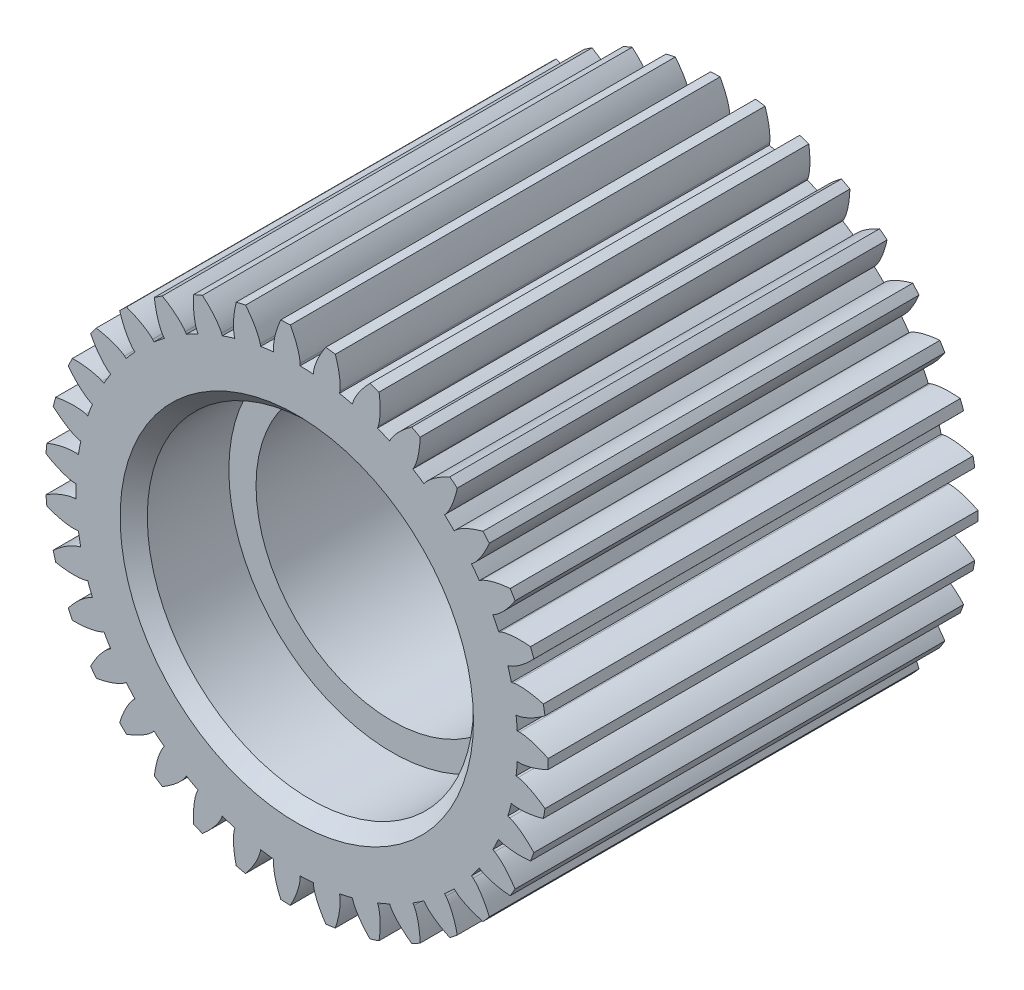
SolidWorks part; units mm, degrees
material "PLA"
ref_plane "Front Plane" through (0, 0, 0) normal (0, 0, 1) x (1, 0, 0)
ref_plane "Top Plane" through (0, 0, 0) normal (0, 1, 0) x (1, 0, 0)
ref_plane "Right Plane" through (0, 0, 0) normal (1, 0, 0) x (0, 0, -1)
sketch "Sketch1" plane through (0, 0, 0) normal (0, 0, 1) x (1, 0, 0)
  circle A0 centre (0, 0) radius 14.25
  dimension "D1" = 28.5
extrude "Boss-Extrude1" add sketch "Sketch1" along normal mid plane 19.8651
sketch "Sketch2" plane through (0, 0, 0) normal (0, 0, 1) x (1, 0, 0)
  line L0 (0, 0) -> (13.7487, 0.1878) construction
  line L1 (0, 0) -> (13.75, 0) construction
  line L2 (0, 0) -> (13.7487, -0.1878) construction
  line L3 (12.9171, -0.1764) -> (13.1238, -0.1792)
  line L4 (12.9196, 0.1764) -> (13.1238, 0.1792)
  circle A0 centre (0, 0) radius 13.75 construction
  circle A1 centre (0, 0) radius 12.9208 construction
  circle A2 centre (0, 0) radius 13.125
  circle A3 centre (0, 0) radius 14.25 construction
  circle A4 centre (0, 0) radius 14.25
  spline S0 degree 4 poles (12.9196, 0.1764) (12.924, 0.1766) (12.9364, 0.1771) (12.9597, 0.1789) (12.9978, 0.183) (13.0462, 0.1897) (13.1086, 0.2003) (13.1818, 0.2152) (13.262, 0.2341) (13.3488, 0.2572) (13.4351, 0.2827) (13.5207, 0.3103) (13.6056, 0.3398) (13.708, 0.3778) (13.8301, 0.4265) (13.9716, 0.4882) (14.1308, 0.5636) (14.2914, 0.6462) (14.448, 0.7322) (14.6046, 0.8246) (14.7548, 0.9177) (14.909, 1.0199) (15.0503, 1.117) (15.2064, 1.2318) (15.3317, 1.3261) (15.4945, 1.4568) (15.5899, 1.5359) (15.7006, 1.6305) (15.7492, 1.6737) (15.7792, 1.7002) knots 0 0 0 0 0 0.005377 0.015084 0.028532 0.04661 0.064855 0.092111 0.119476 0.146842 0.174209 0.201575 0.228941 0.256307 0.307035 0.361767 0.4165 0.471232 0.525964 0.580697 0.635429 0.690161 0.744894 0.799626 0.854358 0.909091 0.954545 1 1 1 1 1 construction
  spline S1 degree 4 poles (12.9196, 0.1764) (12.924, 0.1766) (12.9364, 0.1771) (12.9597, 0.1789) (12.9978, 0.183) (13.0462, 0.1897) (13.1086, 0.2003) (13.1818, 0.2152) (13.262, 0.2341) (13.3488, 0.2572) (13.4351, 0.2827) (13.5207, 0.3103) (13.6056, 0.3398) (13.708, 0.3778) (13.8301, 0.4265) (13.9716, 0.4882) (14.1308, 0.5636) (14.2914, 0.6462) (14.448, 0.7322) (14.6046, 0.8246) (14.7548, 0.9177) (14.909, 1.0199) (15.0503, 1.117) (15.2064, 1.2318) (15.3317, 1.3261) (15.4592, 1.4285) (15.521, 1.479) (15.5524, 1.5052) knots 0 0 0 0 0 0.005377 0.015084 0.028532 0.04661 0.064855 0.092111 0.119476 0.146842 0.174209 0.201575 0.228941 0.256307 0.307035 0.361767 0.4165 0.471232 0.525964 0.580697 0.635429 0.690161 0.744894 0.799626 0.854358 0.909091 0.909091 0.909091 0.909091 0.909091
  spline S2 degree 4 poles (12.9171, -0.1764) (12.9215, -0.1765) (12.9339, -0.1771) (12.9573, -0.1789) (12.9954, -0.1829) (13.0438, -0.1897) (13.1062, -0.2003) (13.1794, -0.2152) (13.2595, -0.234) (13.3464, -0.2572) (13.4326, -0.2827) (13.5182, -0.3103) (13.6031, -0.3397) (13.7055, -0.3777) (13.8276, -0.4265) (13.9692, -0.4882) (14.1283, -0.5635) (14.2889, -0.6462) (14.4456, -0.7322) (14.6021, -0.8245) (14.7524, -0.9177) (14.9065, -1.0199) (15.0479, -1.117) (15.204, -1.2317) (15.3293, -1.3261) (15.492, -1.4568) (15.5874, -1.5358) (15.6981, -1.6305) (15.7468, -1.6737) (15.7768, -1.7002) knots 0 0 0 0 0 0.005377 0.015084 0.028532 0.04661 0.064855 0.092111 0.119476 0.146842 0.174209 0.201575 0.228941 0.256307 0.307035 0.361767 0.4165 0.471232 0.525964 0.580697 0.635429 0.690161 0.744894 0.799626 0.854358 0.909091 0.954545 1 1 1 1 1 construction
  spline S3 degree 4 poles (12.9171, -0.1764) (12.9215, -0.1765) (12.9339, -0.1771) (12.9573, -0.1789) (12.9954, -0.1829) (13.0438, -0.1897) (13.1062, -0.2003) (13.1794, -0.2152) (13.2595, -0.234) (13.3464, -0.2572) (13.4326, -0.2827) (13.5182, -0.3103) (13.6031, -0.3397) (13.7055, -0.3777) (13.8276, -0.4265) (13.9692, -0.4882) (14.1283, -0.5635) (14.2889, -0.6462) (14.4456, -0.7322) (14.6021, -0.8245) (14.7524, -0.9177) (14.9065, -1.0199) (15.0479, -1.117) (15.204, -1.2317) (15.3293, -1.3261) (15.4568, -1.4284) (15.5185, -1.479) (15.5499, -1.5051) knots 0 0 0 0 0 0.005377 0.015084 0.028532 0.04661 0.064855 0.092111 0.119476 0.146842 0.174209 0.201575 0.228941 0.256307 0.307035 0.361767 0.4165 0.471232 0.525964 0.580697 0.635429 0.690161 0.744894 0.799626 0.854358 0.909091 0.909091 0.909091 0.909091 0.909091
  dimension "D1" = 27.5
  dimension "D2" = 25.8415
  dimension "D3" = 26.25
  dimension "D4" = 0.782
  dimension "D5" = 0.782
extrude "Cut-Extrude1" cut sketch "Sketch2" against normal through all both and the other way through all contours A2 A4 region at (13.7878, -0.0005, 0)
pattern_circular "CirPattern2" count 55 over 360 about axis through (0, 0, 9.9326) along (0, 0, -1) of "Cut-Extrude1"
sketch "Sketch3" plane through (0, 0, 9.9326) normal (0, 0, 1) x (1, 0, 0)
  circle A0 centre (0, 0) radius 5
  dimension "D1" = 10
sketch "Sketch4" plane through (0, 0, -9.9326) normal (0, 0, -1) x (-1, 0, 0)
  circle A0 centre (0, 0) radius 9.25
  dimension "D1" = 18.5
extrude "Boss-Extrude2" add sketch "Sketch4" along normal blind 15.8109
sketch "Sketch5" plane through (0, 0, -25.7434) normal (0, 0, -1) x (-1, 0, 0)
  line L0 (0, 0) -> (9.25, 0) construction
  line L1 (0, 0) -> (9.2458, 0.2772) construction
  line L2 (0, 0) -> (9.2458, -0.2772) construction
  line L3 (8.1981, 0.2458) -> (8.1213, 0.2435)
  line L4 (8.1981, -0.2458) -> (8.1213, -0.2435)
  circle A0 centre (0, 0) radius 8.2223 construction
  circle A1 centre (0, 0) radius 8.125
  arc A2 (9.2269, -0.6536) -> (9.2269, 0.6536) centre (0, 0) ccw
  spline S0 degree 4 poles (8.1981, 0.2458) (8.2009, 0.2459) (8.2088, 0.2464) (8.2237, 0.2478) (8.2479, 0.2508) (8.2927, 0.2578) (8.3462, 0.2687) (8.4062, 0.2834) (8.4704, 0.3017) (8.525, 0.3188) (8.5792, 0.3372) (8.633, 0.3569) (8.6977, 0.3821) (8.7749, 0.4144) (8.8643, 0.4551) (8.9648, 0.5047) (9.0661, 0.559) (9.1649, 0.6153) (9.2636, 0.6757) (9.3582, 0.7365) (9.4552, 0.8032) (9.5441, 0.8664) (9.6423, 0.941) (9.721, 1.0024) (9.8232, 1.0872) (9.8831, 1.1385) (9.9525, 1.1999) (9.983, 1.2279) (10.0018, 1.2451) knots 0 0 0 0 0 0.005377 0.015084 0.028532 0.04661 0.092111 0.119476 0.146842 0.174209 0.201575 0.228941 0.256307 0.307035 0.361767 0.4165 0.471232 0.525964 0.580697 0.635429 0.690161 0.744894 0.799626 0.854358 0.909091 0.954545 1 1 1 1 1 construction
  spline S1 degree 4 poles (8.1981, 0.2458) (8.2009, 0.2459) (8.2088, 0.2464) (8.2237, 0.2478) (8.2479, 0.2508) (8.2927, 0.2578) (8.3462, 0.2687) (8.4062, 0.2834) (8.4704, 0.3017) (8.525, 0.3188) (8.5792, 0.3372) (8.633, 0.3569) (8.6977, 0.3821) (8.7749, 0.4144) (8.8643, 0.4551) (8.9648, 0.5047) (9.0661, 0.559) (9.1649, 0.6153) (9.2636, 0.6757) (9.3582, 0.7365) (9.4552, 0.8032) (9.5441, 0.8664) (9.6423, 0.941) (9.721, 1.0024) (9.8011, 1.0688) (9.8398, 1.1016) (9.8596, 1.1186) knots 0 0 0 0 0 0.005377 0.015084 0.028532 0.04661 0.092111 0.119476 0.146842 0.174209 0.201575 0.228941 0.256307 0.307035 0.361767 0.4165 0.471232 0.525964 0.580697 0.635429 0.690161 0.744894 0.799626 0.854358 0.909091 0.909091 0.909091 0.909091 0.909091
  spline S2 degree 4 poles (8.1981, -0.2458) (8.2009, -0.2459) (8.2088, -0.2464) (8.2237, -0.2478) (8.2479, -0.2508) (8.2927, -0.2578) (8.3462, -0.2687) (8.4062, -0.2834) (8.4704, -0.3017) (8.525, -0.3188) (8.5792, -0.3372) (8.633, -0.3569) (8.6977, -0.3821) (8.7749, -0.4144) (8.8643, -0.4551) (8.9648, -0.5047) (9.0661, -0.559) (9.1649, -0.6153) (9.2636, -0.6757) (9.3582, -0.7365) (9.4552, -0.8032) (9.5441, -0.8664) (9.6423, -0.941) (9.721, -1.0024) (9.8232, -1.0872) (9.8831, -1.1385) (9.9525, -1.1999) (9.983, -1.2279) (10.0018, -1.2451) knots 0 0 0 0 0 0.005377 0.015084 0.028532 0.04661 0.092111 0.119476 0.146842 0.174209 0.201575 0.228941 0.256307 0.307035 0.361767 0.4165 0.471232 0.525964 0.580697 0.635429 0.690161 0.744894 0.799626 0.854358 0.909091 0.954545 1 1 1 1 1 construction
  spline S3 degree 4 poles (8.1981, -0.2458) (8.2009, -0.2459) (8.2088, -0.2464) (8.2237, -0.2478) (8.2479, -0.2508) (8.2927, -0.2578) (8.3462, -0.2687) (8.4062, -0.2834) (8.4704, -0.3017) (8.525, -0.3188) (8.5792, -0.3372) (8.633, -0.3569) (8.6977, -0.3821) (8.7749, -0.4144) (8.8643, -0.4551) (8.9648, -0.5047) (9.0661, -0.559) (9.1649, -0.6153) (9.2636, -0.6757) (9.3582, -0.7365) (9.4552, -0.8032) (9.5441, -0.8664) (9.6423, -0.941) (9.721, -1.0024) (9.8011, -1.0688) (9.8398, -1.1016) (9.8596, -1.1186) knots 0 0 0 0 0 0.005377 0.015084 0.028532 0.04661 0.092111 0.119476 0.146842 0.174209 0.201575 0.228941 0.256307 0.307035 0.361767 0.4165 0.471232 0.525964 0.580697 0.635429 0.690161 0.744894 0.799626 0.854358 0.909091 0.909091 0.909091 0.909091 0.909091
  dimension "D2" = 16.25
  dimension "D3" = 18.5
  dimension "D1" = 16.4446
  dimension "D4" = 1.717
  dimension "D5" = 1.717
extrude "Cut-Extrude2" cut sketch "Sketch5" against normal up to surface (15.8109 mm away) contours A2 A1 region at (-8.7837, 0, -25.7434) up to face at (9.25, 0, -9.9326)
pattern_circular "CirPattern3" count 35 over 360 about axis through (0, 0, -25.7434) along (0, 0, 1) of "Cut-Extrude2"
extrude "Cut-Extrude3" cut sketch "Sketch3" against normal through all contours A0
sketch "Sketch7" plane through (0, 0, -25.7434) normal (0, 0, -1) x (-1, 0, 0)
  circle A0 centre (0, 0) radius 6
  dimension "D1" = 12
extrude "Cut-Extrude4" cut sketch "Sketch7" against normal blind 3.5
ref_plane "Plane1" through (0, 0, -7.9054) normal (0, 0, -1) x (-1, 0, 0)
mirror "Mirror1" [suppressed] about plane through (0, 0, -7.9054) normal (0, 0, -1)
sketch "Sketch8" plane through (0, 0, 9.9326) normal (0, 0, 1) x (1, 0, 0)
  circle A0 centre (0, 0) radius 16.2595
extrude "Cut-Extrude5" cut sketch "Sketch8" against normal up to surface (19.8651 mm away) up to face at (0, 0, -9.9326)
ref_plane "Plane2" through (0, 0, -17.838) normal (0, 0, -1) x (-1, 0, 0)
mirror "Mirror3" about plane through (0, 0, -17.838) normal (0, 0, -1) of "Cut-Extrude4"
chamfer "Chamfer1" distance 0.5 angle 45 2 edges at (-6, 0, -25.7434) (-6, 0, -9.9326)
equation "\"module\" = 0.5"
equation "\"pressure angle\" = 20.0"
equation "\"h_a\" = 0.5"
equation "\"h_b\" = 0.625"
equation "\"clr_tip_root\" = 0.125"
equation "\"D1@Sketch1\" = \"dp_p_b\" + 2 * \"h_a\""
equation "\"D1@Boss-Extrude1\"=\"fw_p_b\" -  \"standard_clearance_1_5mm\""
equation "\"D1@Sketch2\" = \"dp_p_b\""
equation "\"D2@Sketch2\"= \"db_p_b\""
equation "\"D3@Sketch2\" = \"dp_p_b\" - 2 * \"h_b\""
equation "\"Nr_s\" = 170"
equation "\"pressure_angle\" = 20.0"
equation "\"h_f\" = 0.625"
equation "\"dp_r_s\" = 85.0"
equation "\"bearing_ID\" = 75"
equation "\"bearing_OD\" = 95"
equation "\"bearing_height\" = 10"
equation "\"clearance_planet\" = 1.5"
equation "\"case_dist\" = 6.5"
equation "\"Motor_case_OD_max\" = 131.3"
equation "\"case_mounting_PCD\" = 123.8"
equation "\"bearing mount thickness\" = 8"
equation "\"case_mounting_hole_dia\" = 3"
equation "\"output_mounting_PCD\" = 103"
equation "\"output_mounting_hole_dia\" = 4"
equation "\"clearance_case_mount_holes_shell_thickness\" = 1"
equation "\"motor_case_OD_base\" = 121.8"
equation "\"sec_carrier_thickness\" = 5"
equation "\"sun_coupler_hub_thickness\" = 4"
equation "\"clearance_sun_coupler_sec_carrier\" = 1.5"
equation "\"clearance_motor_and_case\" = 5"
equation "\"motor_OD\" = 106.8"
equation "\"Motor_case_thickness\" = 2.5"
equation "\"Motor_case_ID\" = 116.8"
equation "\"case_mounting_hole_shift\" = 1.0"
equation "\"output_mounting_nut_wrench_size\" = 7"
equation "\"output_mounting_nut_thickness\" = 3.2"
equation "\"case_mounting_hole_allen_socket_dia\" = 5.5"
equation "\"output_mounting_nut_depth\" = 3"
equation "\"case_mounting_bolt_depth\" = 4.5"
equation "\"Ns\" = 80"
equation "\"ring_radial_thickness\" = 5"
equation "\"ring_to_chamfer_clearance\" = 1.5"
equation "\"Motor_case_OD_base_to_chamfer\" = 5"
equation "\"pattern_offset_from_motor_case_OD_base\" = 3"
equation "\"pattern_bulge_dia\" = 3"
equation "\"pattern_num_bulge\" = 18"
equation "\"pattern_depth\" = 2"
equation "\"motor_height\" = 47.6"
equation "\"case_mounting_wrench_size\" = 5.5"
equation "\"case_mounting_nut_clearance\" = 2"
equation "\"base_plate_thickness\" = 4"
equation "\"case_mounting_nut_thickness\" = 2.4"
equation "\"case_mounting_surface_height\" = 4"
equation "\"motor_mount_hole_PCD\" = 40"
equation "\"motor_mount_hole_dia\" = 5"
equation "\"motor_mount_hole_num\" = 4"
equation "\"central_hole_offset_from_motor_mount_PCD\" = 5"
equation "\"wire_slot_dist_from_center\" = 45.5"
equation "\"wire_slot_length\" = 10"
equation "\"wire_slot_radius\" = 3"
equation "\"driver_upper_holes_dist_from_center\" = 29"
equation "\"driver_lower_holes_dist_from_center\" = 13"
equation "\"driver_side_holes_dist_from_center\" = 22.5"
equation "\"driver_mount_holes_dia\" = 3"
equation "\"driver_mount_inserts_OD\" = 4.8"
equation "\"driver_mount_thickness\" = 1.5"
equation "\"driver_mount_height\" = 6"
equation "\"air_flow_hole_offset\" = 3"
equation "\"num_planet\" = 5"
equation "\"planet_pin_bolt_dia\" = 5"
equation "\"planet_pin_socket_head_dia\" = 8.5"
equation "\"carrier_PCD\" = 67.5"
equation "\"planet_shaft_dia\" = 8"
equation "\"planet_shaft_step_offset\" = 1"
equation "\"carrier_trapezoidal_support_sun_offset\" = 5"
equation "\"carrier_trapezoidal_support_hole_PCD_offset_bearing_ID\" = 4"
equation "\"carrier_trapezoidal_support_hole_dia\" = 3"
equation "\"carrier_trapezoidal_support_hole_socket_head_dia\" = 5.5"
equation "\"carrier_bearing_step_width\" = 1.5"
equation "\"standard_clearance_1_5mm\" = 1.5"
equation "\"standard_fillet_1_5mm\" = 1.5"
equation "\"sun_shaft_bearing_OD\" = 16"
equation "\"sun_shaft_bearing_width\" = 5"
equation "\"standard_bearing_insertion_chamfer\" = 0.5"
equation "\"carrier_trapezoidal_support_hole_wrench_size\" = 5.5"
equation "\"planet_pin_bolt_wrench_size\" = 8"
equation "\"planet_bearing_OD\" = 12"
equation "\"planet_bearing_width\" = 3.5"
equation "\"planet_bore\" = 10"
equation "\"D1@Sketch3\"=\"planet_bore\""
equation "\"Np_b\" = 55"
equation "\"dp_s\" = 40.0"
equation "\"db_s\" = 37.58770483143634"
equation "\"fw_s_calc\" = 4.872946430626146"
equation "\"alpha_s\" = 0.8539582918412272"
equation "\"beta_s\" = 0.5420834163175456"
equation "\"dp_p_b\" = 27.5"
equation "\"db_p_b\" = 25.84154707161248"
equation "\"fw_p_s\" = 15.81085678360617"
equation "\"alpha_p_b\" = 0.8539582918412449"
equation "\"beta_p_b\" = 1.564810689044783"
equation "\"motor_output_hole_PCD\" = 23"
equation "\"motor_output_hole_dia\" = 4"
equation "\"motor_output_hole_num\" = 4"
equation "\"sun_shaft_bearing_ID\" = 8"
equation "\"sun_hub_dia\" = 30.0"
equation "\"sun_central_bolt_dia\" = 5"
equation "\"sun_central_bolt_socket_head_dia\" = 8.5"
equation "\"fw_s_used\" = 44.67596466627659"
equation "\"motor_output_hole_CSK_OD\" = 8"
equation "\"motor_output_hole_CSK_head_height\" = 2.0"
equation "\"bearing_retainer_thickness\" = 2"
equation "\"Np_s\" = 35"
equation "\"fw_p_b\" = 21.365107882670422"
equation "\"dp_p_s\" = 17.5"
equation "\"db_p_s\" = 16.444620863753396"
equation "\"alpha_p_s\" = 0.8539582918412556"
equation "\"beta_p_s\" = 3.434940559174632"
equation "\"D1@Sketch4\"=\"dp_p_s\" + 2 * \"h_a\""
equation "\"D1@Boss-Extrude2\"=\"fw_p_s\""
equation "\"D2@Sketch5\"=\"dp_p_s\" - 2 * \"h_b\""
equation "\"D3@Sketch5\"=\"dp_p_s\"+2 * \"h_a\" "
equation "\"D1@Sketch5\"=\"db_p_s\""
equation "\"D1@CirPattern3\"=\"Np_s\""
equation "\"D4@Sketch5\"=\"beta_p_s\"/2"
equation "\"D5@Sketch5\"=\"beta_p_s\"/2"
equation "\"D4@Sketch2\"=\"beta_p_b\"/2"
equation "\"D5@Sketch2\"=\"beta_p_b\"/2"
equation "\"D1@Sketch7\"=\"planet_bearing_OD\""
equation "\"D1@Cut-Extrude4\"=\"planet_bearing_width\""
equation "\"D1@Chamfer1\"=\"standard_bearing_insertion_chamfer\""
equation "\"D1@CirPattern2\"=\"Np_b\""
equation "\"Nr_b\" = 190"
equation "\"dp_r_b\" = 95.0"
equation "\"db_r_b\" = 89.2707989746613"
equation "\"fw_r_b\" = 21.365107882670422"
equation "\"alpha_r_b\" = 0.8539582918412414"
equation "\"beta_r_b\" = 2.655285004735114"
equation "\"ring_OD_b\" = 105.0"
equation "\"Fillet10\"= IIF ( \"ring_OD_b\" > ( \"bearing_OD\" + 2 * \"bearing mount thickness\" ) , \"suppressed\" , \"unsuppressed\" )"
equation "\"Fillet11\"= IIF ( \"ring_OD_b\" < ( \"bearing_OD\" + 2 * \"bearing mount thickness\" ) , \"suppressed\" , \"unsuppressed\" )"
equation "\"clr_tip_root_s\" = 0.125"
equation "\"db_r_s\" = 79.87387276680222"
equation "\"fw_r_s\" = 14.31085678360617"
equation "\"alpha_r_s\" = 0.8539582918412307"
equation "\"beta_r_s\" = 2.766740113094226"
equation "\"small_ring_case_thickness\" = 4"
equation "\"carrier_thickness\" = 4"
equation "\"small_ring_output_wall_thickness\" = 5"
equation "\"small_ring_output_wall_to_bearing_shaft_attachement_hole_dia\" = 4"
equation "\"small_ring_output_wall_to_bearing_shaft_attachement_hole_depth\" = 6.5"
equation "\"small_ring_output_wall_to_bearing_shaft_attachement_nut_wrench\" = 7"
equation "\"small_ring_output_wall_to_bearing_shaft_attachement_nut_thickness\" = 3.2"
equation "\"small_ring_output_wall_to_bearing_shaft_attachement_hole_pcd\" = 12"
equation "\"small_ring_output_wall_to_bearing_shaft_attachement_hole_num\" = 3"
equation "\"small_ring_output_wall_to_bearing_shaft_attachement_hole_CSK_OD\" = 8"
equation "\"small_ring_output_wall_to_bearing_shaft_attachement_hole_CSK_head_height\" = 2.0"
equation "\"carrier_small_ring_inner_bearing_ID\" = 20"
equation "\"carrier_small_ring_inner_bearing_OD\" = 32"
equation "\"carrier_small_ring_inner_bearing_height\" = 7"
equation "\"carrier_small_ring_inner_bearing_flap\" = 2"
equation "\"gear_casing_big_ring_to_bearing_dist\" = 24.81085678360617"
equation "\"gear_casing_thickness\" = 4"
